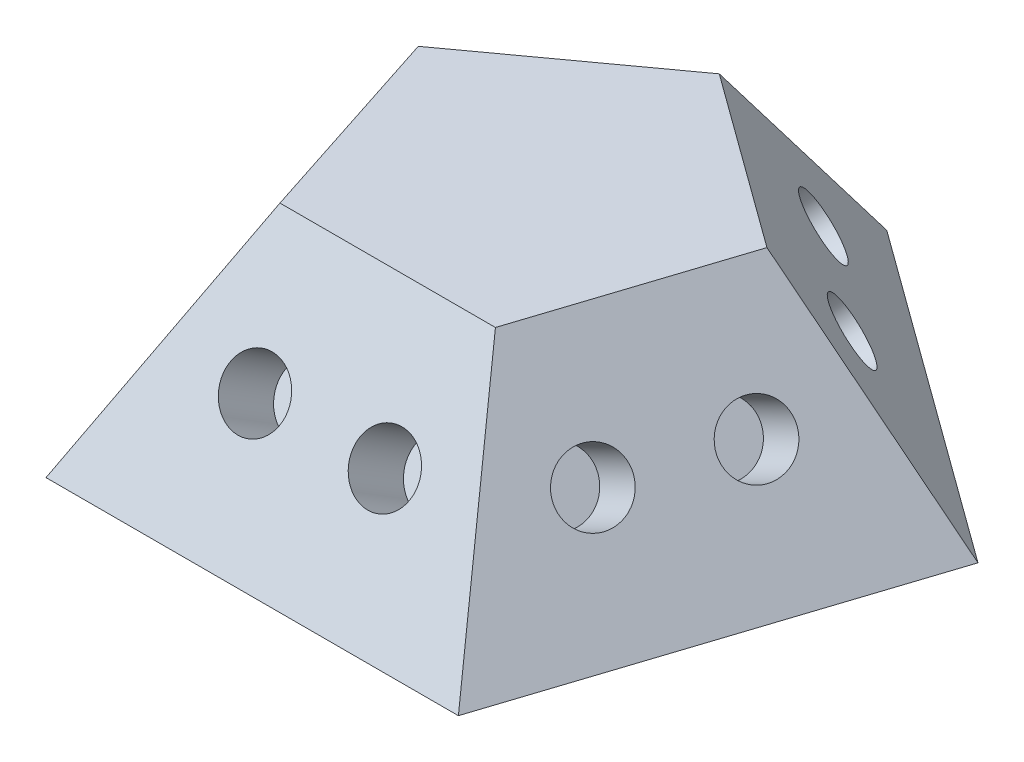
SolidWorks part; units mm, degrees
ref_plane "Front Plane" through (0, 0, 0) normal (0, 0, 1) x (1, 0, 0)
ref_plane "Top Plane" through (0, 0, 0) normal (0, 1, 0) x (1, 0, 0)
ref_plane "Right Plane" through (0, 0, 0) normal (1, 0, 0) x (0, 0, -1)
ref_axis "Axis1" through (0, 14.8487, 0) along (0, -1, 0)
sketch "Sketch1" plane through (0, 0, 0) normal (0, 1, 0) x (1, 0, 0)
  line L1 (0, 10.8033) -> (-10.2745, 3.3384)
  line L2 (-10.2745, 3.3384) -> (-6.35, -8.74)
  line L3 (-6.35, -8.74) -> (6.35, -8.74)
  line L4 (6.35, -8.74) -> (10.2745, 3.3384)
  line L5 (10.2745, 3.3384) -> (0, 10.8033)
  circle A0 centre (0, 0) radius 8.74 construction
  dimension "D1" = 12.7
extrude "Boss-Extrude1" add sketch "Sketch1" along normal blind 6.752 draft 31.717
sketch "Sketch3" plane through (0, 3.9087, 6.3243) normal (0, 0.5257, 0.8507) x (1, 0, 0)
  line L0 (-2, -0.6262) -> (2, -0.6262) construction
  line L1 (-6.35, -4.5949) -> (6.35, -4.5949) construction
  line L2 (-2, -4.5949) -> (-2, 3.3426) construction
  circle A0 centre (-2, -0.6262) radius 1
  circle A1 centre (2, -0.6262) radius 1
  point P4 (0, -0.6262)
  point P5 (-2, -0.6262)
  dimension "D1" = 2
  dimension "D2" = 4
  dimension "D3" = 7.9375
extrude "Cut-Extrude1" cut sketch "Sketch3" against normal blind 2
pattern_circular "CirPattern1" count 5 over 360 about axis through (0, 14.8487, 0) along (0, -1, 0) of "Cut-Extrude1"
equation "\"angle\"= arccos ( - sqr ( 5 ) / 5 )"
equation "\"theta\"= 90 - \"angle\" / 2"
equation "\"side\"=0.5"
equation "\"D1@Sketch1\"=\"side\""
equation "\"D3@Boss-Extrude1\"=\"theta\""
equation "\"D1@Boss-Extrude1\"=\"height\""
equation "\"face_height\"= .3125in"
equation "\"height\"= \"face_height\" * cos ( \"theta\" )"
equation "\"D3@Sketch3\"=\"face_height\""
